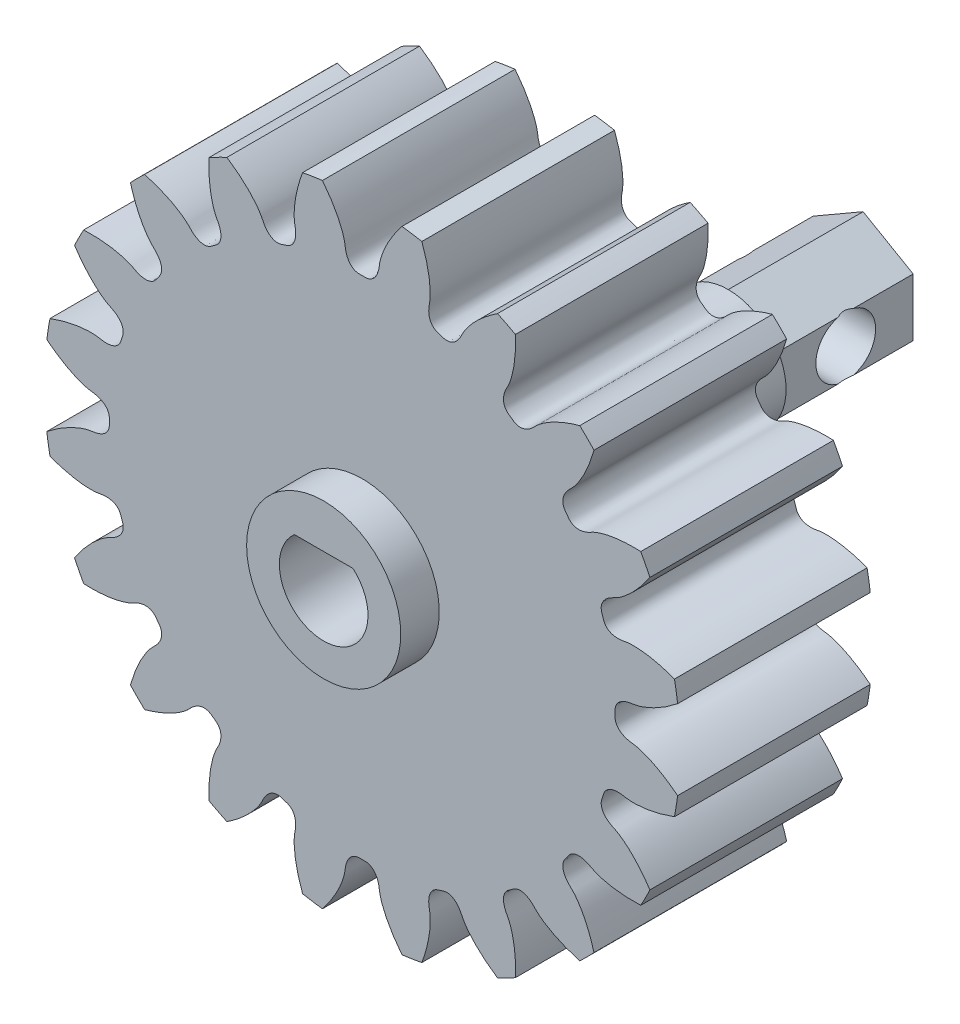
SolidWorks part; units mm, degrees
ref_plane "Front Plane" through (0, 0, 0) normal (0, 0, 1) x (1, 0, 0)
ref_plane "Top Plane" through (0, 0, 0) normal (0, 1, 0) x (1, 0, 0)
ref_plane "Right Plane" through (0, 0, 0) normal (1, 0, 0) x (0, 0, -1)
ref_axis "Axis1" through (0, 0, 55) along (0, 0, -1)
sketch "SketchRevolveSpurAssembly01Pinion" plane through (0, 0, 0) normal (1, 0, 0) x (0, 0, -1)
  line L0 (0, 0) -> (1, 0) construction
  line L1 (-5, 0) -> (-5, 16.5)
  line L2 (-5, 16.5) -> (5, 16.5)
  line L3 (5, 16.5) -> (5, 0)
  line L4 (5, 0) -> (-5, 0)
  dimension "Side1" = 5
  dimension "OutsideRadius" = 16.5
  dimension "Side2" = 5
revolve "SpurAssembly01Pinion" add sketch "SketchRevolveSpurAssembly01Pinion" angle 360 about L0
sketch "SketchToothSpurAssembly01Pinion" plane through (0, 0, 0) normal (0, 0, 1) x (1, 0, 0)
  arc A0 (16.4388, 2.1204) -> (16.4388, -2.1204) centre (0, 0) cw
  spline S0 degree 3 poles (16.4388, -2.1204) (16.3062, -2.0126) (16.1079, -1.8609) (15.8417, -1.6767) (15.6549, -1.5557) (15.4759, -1.4476) (15.3054, -1.3516) (15.1441, -1.2672) (14.9923, -1.1937) (14.8506, -1.1305) (14.7196, -1.0767) (14.5996, -1.0318) (14.491, -0.9949) (14.3942, -0.9653) (14.3096, -0.9423) (14.2375, -0.925) (14.178, -0.9126) (14.0492, -0.8903) (13.9123, -0.8782) (13.7697, -0.8427) (13.6956, -0.8206) (13.6244, -0.795) (13.5557, -0.7654) (13.4893, -0.7311) (13.4248, -0.6913) (13.3623, -0.6446) (13.3021, -0.5892) (13.2452, -0.523) (13.1943, -0.4439) (13.1533, -0.3509) (13.1303, -0.2534) (13.1208, -0.135) (13.1277, 0) (13.1208, 0.135) (13.1303, 0.2534) (13.1533, 0.3509) (13.1943, 0.4439) (13.2452, 0.523) (13.3021, 0.5892) (13.3623, 0.6446) (13.4248, 0.6913) (13.4893, 0.7311) (13.5557, 0.7654) (13.6244, 0.795) (13.6956, 0.8206) (13.7697, 0.8427) (13.9123, 0.8782) (14.0492, 0.8903) (14.178, 0.9126) (14.2375, 0.925) (14.3096, 0.9423) (14.3942, 0.9653) (14.491, 0.9949) (14.5996, 1.0318) (14.7196, 1.0767) (14.8506, 1.1305) (14.9923, 1.1937) (15.1441, 1.2672) (15.3054, 1.3516) (15.4759, 1.4476) (15.6549, 1.5557) (15.8417, 1.6767) (16.1079, 1.8609) (16.3062, 2.0126) (16.4388, 2.1204) knots 0 0 0 0 0.061423 0.08971 0.11638 0.141434 0.164872 0.186693 0.206898 0.225486 0.242459 0.257814 0.271554 0.283677 0.294183 0.303073 0.310347 0.316004 0.350077 0.359568 0.368803 0.377844 0.386769 0.395676 0.404689 0.413963 0.423683 0.434051 0.445256 0.457401 0.47042 0.481067 0.5 0.518933 0.52958 0.542599 0.554744 0.565949 0.576317 0.586037 0.595311 0.604324 0.613231 0.622156 0.631197 0.640432 0.649923 0.683996 0.689653 0.696927 0.705817 0.716323 0.728446 0.742186 0.757541 0.774514 0.793102 0.813307 0.835128 0.858566 0.88362 0.91029 0.938577 1 1 1 1
extrude "ToothExtrudeCutSpurAssembly01Pinion" cut sketch "SketchToothSpurAssembly01Pinion" against normal blind 5 and the other way blind 5
pattern_circular "PatternSpurAssembly01Pinion" count 20 every 18 about axis through (0, 0, 55) along (0, 0, -1) of "ToothExtrudeCutSpurAssembly01Pinion"
sketch "AuxiliarySketchSpurAssembly01Pinion" plane through (0, 0, 0) normal (0, 0, 1) x (1, 0, 0)
  circle A0 centre (0, 0) radius 15 construction
  circle A1 centre (0, 0) radius 14.0954 construction
  circle A2 centre (0, 0) radius 14.1048 construction
  circle A3 centre (0, 0) radius 16.5 construction
  circle A4 centre (0, 0) radius 13.125 construction
  dimension "PitchDiameter" = 30
  dimension "BaseDiameter" = 28.1908
  dimension "FormDiameter" = 28.2095
  dimension "MajorDiameter" = 33
  dimension "MinorDiameter" = 26.25
sketch "Sketch2" plane through (0, 0, -5) normal (0, 0, -1) x (-1, 0, 0)
  circle A0 centre (0, 0) radius 3
extrude "Boss-Extrude1" add sketch "Sketch2" along normal blind 9
sketch "Sketch3" plane through (0, 0, -14) normal (0, 0, -1) x (-1, 0, 0)
  line L0 (0, 3) -> (-2.5981, 1.5)
  line L1 (-2.5981, 1.5) -> (-2.5981, -1.5)
  line L2 (0, -3) -> (0, 3) construction
  line L3 (-2.5981, -1.5) -> (2.5981, 1.5) construction
  line L4 (2.5981, -1.5) -> (-2.5981, 1.5) construction
  line L5 (-2.5981, -1.5) -> (0, -3)
  line L6 (0, -3) -> (2.5981, -1.5)
  line L7 (2.5981, -1.5) -> (2.5981, 1.5)
  line L8 (2.5981, 1.5) -> (0, 3)
  circle A0 centre (0, 0) radius 3 construction
  point P11 (0, 0)
  point P15 (0, 0)
  point P18 (0, 0)
extrude "Boss-Extrude2" add sketch "Sketch3" along normal blind 7
sketch "Sketch4" plane through (2.5981, 0, 0) normal (1, 0, 0) x (0, 0, -1)
  line L0 (14, 1.5) -> (21, -1.5) construction
  circle A0 centre (17.5, 0) radius 1.55
extrude "Cut-Extrude3" cut sketch "Sketch4" against normal up to surface (5.1962 mm away) up to face at (-2.5981, 0, -17.5)
sketch "Sketch5" plane through (0, 0, 5) normal (0, 0, 1) x (1, 0, 0)
  circle A0 centre (0, 0) radius 4
extrude "Boss-Extrude3" add sketch "Sketch5" along normal blind 2
sketch "Sketch6" plane through (0, 0, 7) normal (0, 0, 1) x (1, 0, 0)
  line L0 (0, 0) -> (0, 1.725) construction
  line L1 (-1.5213, 1.725) -> (1.5213, 1.725)
  circle A0 centre (0, 0) radius 2.3 construction
  arc A1 (1.5213, 1.725) -> (-1.5213, 1.725) centre (0, 0) cw
  point P7 (0, 1.725)
extrude "Cut-Extrude4" cut sketch "Sketch6" against normal blind 8
